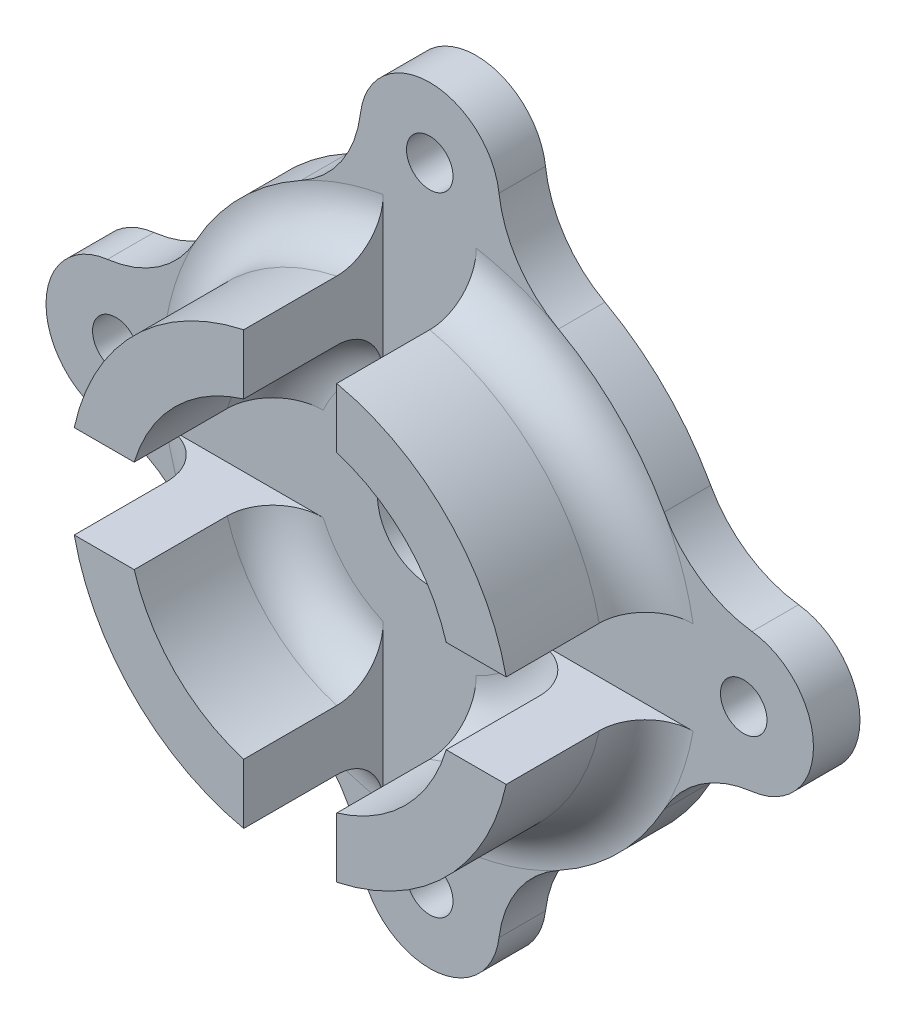
SolidWorks part; units mm, degrees
ref_plane "Front Plane" through (0, 0, 0) normal (0, 0, 1) x (1, 0, 0)
ref_plane "Top Plane" through (0, 0, 0) normal (0, 1, 0) x (1, 0, 0)
ref_plane "Right Plane" through (0, 0, 0) normal (1, 0, 0) x (0, 0, -1)
sketch "Sketch2" plane through (0, 0, 0) normal (0, 0, 1) x (1, 0, 0)
  line L0 (0, 9.5) -> (0, 0) construction
  line L1 (-2, 9.5) -> (-2, 0)
  line L2 (2, 9.5) -> (2, 0)
  line L3 (9.5, 2) -> (0, 2)
  line L4 (9.5, -2) -> (0, -2)
  line L5 (2, -9.5) -> (2, 0)
  line L6 (-2, -9.5) -> (-2, 0)
  line L7 (-9.5, -2) -> (0, -2)
  line L8 (-9.5, 2) -> (0, 2)
  circle A0 centre (0, 0) radius 2.25 construction
  circle A1 centre (0, 0) radius 9.5 construction
  circle A2 centre (0, 0) radius 2.25
  circle A3 centre (0, 0) radius 9.5
  circle A4 centre (0, 0) radius 7
  circle A5 centre (0, -13.5) radius 1 construction
  circle A6 centre (0, -13.5) radius 1
  arc A7 (5.5352, -10.0802) -> (2.9782, -13.8611) centre (7.9418, -14.463) ccw construction
  arc A8 (-2.9782, -13.8611) -> (2.9782, -13.8611) centre (0, -13.5) ccw construction
  arc A9 (-2.9782, -13.8611) -> (-5.5352, -10.0802) centre (-7.9418, -14.463) ccw construction
  arc A10 (-13.8611, 2.9782) -> (-13.8611, -2.9782) centre (-13.5, 0) ccw construction
  arc A11 (-10.0802, -5.5352) -> (-13.8611, -2.9782) centre (-14.463, -7.9418) ccw construction
  arc A12 (-13.8611, 2.9782) -> (-10.0802, 5.5352) centre (-14.463, 7.9418) ccw construction
  arc A13 (-5.5352, 10.0802) -> (-2.9782, 13.8611) centre (-7.9418, 14.463) ccw construction
  arc A14 (2.9782, 13.8611) -> (-2.9782, 13.8611) centre (0, 13.5) ccw construction
  arc A15 (2.9782, 13.8611) -> (5.5352, 10.0802) centre (7.9418, 14.463) ccw construction
  circle A16 centre (0, 0) radius 11.5 construction
  arc A17 (10.0802, 5.5352) -> (13.8611, 2.9782) centre (14.463, 7.9418) ccw construction
  arc A18 (13.8611, -2.9782) -> (10.0802, -5.5352) centre (14.463, -7.9418) ccw construction
  arc A19 (13.8611, -2.9782) -> (13.8611, 2.9782) centre (13.5, 0) ccw construction
  circle A20 centre (13.5, 0) radius 1 construction
  circle A21 centre (0, 13.5) radius 1 construction
  circle A22 centre (-13.5, 0) radius 1 construction
  arc A23 (5.5352, -10.0802) -> (2.9782, -13.8611) centre (7.9418, -14.463) ccw
  arc A24 (-2.9782, -13.8611) -> (2.9782, -13.8611) centre (0, -13.5) ccw
  arc A25 (-2.9782, -13.8611) -> (-5.5352, -10.0802) centre (-7.9418, -14.463) ccw
  arc A26 (-13.8611, 2.9782) -> (-13.8611, -2.9782) centre (-13.5, 0) ccw
  arc A27 (-10.0802, -5.5352) -> (-13.8611, -2.9782) centre (-14.463, -7.9418) ccw
  arc A28 (-13.8611, 2.9782) -> (-10.0802, 5.5352) centre (-14.463, 7.9418) ccw
  arc A29 (-5.5352, 10.0802) -> (-2.9782, 13.8611) centre (-7.9418, 14.463) ccw
  arc A30 (2.9782, 13.8611) -> (-2.9782, 13.8611) centre (0, 13.5) ccw
  arc A31 (2.9782, 13.8611) -> (5.5352, 10.0802) centre (7.9418, 14.463) ccw
  circle A32 centre (0, 0) radius 11.5
  arc A33 (10.0802, 5.5352) -> (13.8611, 2.9782) centre (14.463, 7.9418) ccw
  arc A34 (13.8611, -2.9782) -> (10.0802, -5.5352) centre (14.463, -7.9418) ccw
  arc A35 (13.8611, -2.9782) -> (13.8611, 2.9782) centre (13.5, 0) ccw
  circle A36 centre (13.5, 0) radius 1
  circle A37 centre (0, 13.5) radius 1
  circle A38 centre (-13.5, 0) radius 1
  point P27 (0, 0)
  dimension "D1" = 14
  dimension "D2" = 2
  dimension "D3" = 2
  dimension "D4" = 4
extrude "Boss-Extrude1" add sketch "Sketch2" along normal blind 2 contours A4 L1 A3 L8 | A3 L0 A4 L2 | L0 A3 L1 A4 | A4 L8 A3 L7 | A4 L7 A3 L6 | A4 L6 A3 L5 | A4 L5 A3 L4 | A4 L4 A3 L3 | A4 L3 A3 L2 | L7 A4 L6 | L6 A4 L5 L4 A2 L7 | L5 A4 L4 | L4 A4 L3 L2 A2 L5 | L3 A4 L2 | A4 L0 A2 L3 L2 | L0 A4 L1 L8 A2 | L1 A4 L8 | L8 A4 L7 L6 A2 L1 | A2 L8 L1 | A2 L2 L3 | A2 L4 L5 | A2 L6 L7 | A32 A28 A26 A27 A38 | A32 A25 A24 A23 A6 | A34 A35 A33 A32 A36 | A32 A31 A30 A29 A37 | A32 A3 region at (1.0052, 8.1658, 0) region at (-1.0052, 8.1658, 0) region at (1.001, 4.495, 0) region at (-1.001, 4.495, 0) region at (5.6126, 5.6126, 0) region at (-5.6126, 5.6126, 0) region at (3.8302, 3.8302, 0) region at (-3.8302, 3.8302, 0) region at (8.1658, 0, 0) region at (-8.1658, 0, 0) region at (1.7116, 1.7116, 0) region at (-1.7116, 1.7116, 0) region at (4.495, 0, 0) region at (-4.495, 0, 0) region at (-5.6126, -5.6126, 0) region at (-3.8302, -3.8302, 0) region at (5.6126, -5.6126, 0) region at (0, -8.1658, 0) region at (-1.7116, -1.7116, 0) region at (3.8302, -3.8302, 0) region at (0, -4.495, 0) region at (1.7116, -1.7116, 0) region at (3.6941, -11.5902, 0) region at (0, -11.1747, 0) region at (11.2634, -2.889, 0) region at (-11.5902, -3.6941, 0) region at (-3.6941, 11.5902, 0)
sketch "Sketch3" plane through (0, 0, 2) normal (0, 0, 1) x (1, 0, 0)
  line L0 (9.5, 2) -> (0, 2) construction
  line L1 (-9.5, 2) -> (0, 2) construction
  line L2 (2, 9.5) -> (2, 0) construction
  line L3 (2, -9.5) -> (2, 0) construction
  line L4 (-2, 9.5) -> (-2, 0) construction
  line L5 (-2, -9.5) -> (-2, 0) construction
  line L6 (9.5, -2) -> (0, -2) construction
  line L7 (-9.5, -2) -> (0, -2) construction
  line L8 (9.5, 2) -> (0, 2)
  line L9 (-9.5, 2) -> (0, 2)
  line L10 (2, 9.5) -> (2, 0)
  line L11 (2, -9.5) -> (2, 0)
  line L12 (-2, 9.5) -> (-2, 0)
  line L13 (-2, -9.5) -> (-2, 0)
  line L14 (9.5, -2) -> (0, -2)
  line L15 (-9.5, -2) -> (0, -2)
  arc A0 (5.5352, -10.0802) -> (2.9782, -13.8611) centre (7.9418, -14.463) ccw construction
  circle A1 centre (0, -13.5) radius 1
  circle A2 centre (0, -13.5) radius 1
  circle A3 centre (0, 0) radius 7
  circle A4 centre (0, 0) radius 7
  circle A5 centre (0, 0) radius 9.5
  circle A6 centre (0, 0) radius 9.5
  circle A7 centre (0, 0) radius 2.25
  circle A8 centre (0, 0) radius 2.25
  circle A9 centre (13.5, 0) radius 1
  circle A10 centre (13.5, 0) radius 1
  circle A11 centre (0, 0) radius 11.5
  circle A12 centre (0, 0) radius 11.5
  circle A13 centre (-13.5, 0) radius 1
  circle A14 centre (-13.5, 0) radius 1
  circle A15 centre (0, 13.5) radius 1
  circle A16 centre (0, 13.5) radius 1
  arc A17 (-2.9782, -13.8611) -> (2.9782, -13.8611) centre (0, -13.5) ccw construction
  arc A18 (-2.9782, -13.8611) -> (-5.5352, -10.0802) centre (-7.9418, -14.463) ccw construction
  arc A19 (-5.5352, 10.0802) -> (-2.9782, 13.8611) centre (-7.9418, 14.463) ccw construction
  arc A20 (2.9782, 13.8611) -> (-2.9782, 13.8611) centre (0, 13.5) ccw construction
  arc A21 (2.9782, 13.8611) -> (5.5352, 10.0802) centre (7.9418, 14.463) ccw construction
  arc A22 (-10.0802, -5.5352) -> (-13.8611, -2.9782) centre (-14.463, -7.9418) ccw construction
  arc A23 (-13.8611, 2.9782) -> (-13.8611, -2.9782) centre (-13.5, 0) ccw construction
  arc A24 (-13.8611, 2.9782) -> (-10.0802, 5.5352) centre (-14.463, 7.9418) ccw construction
  arc A25 (10.0802, 5.5352) -> (13.8611, 2.9782) centre (14.463, 7.9418) ccw construction
  arc A26 (13.8611, -2.9782) -> (13.8611, 2.9782) centre (13.5, 0) ccw construction
  arc A27 (13.8611, -2.9782) -> (10.0802, -5.5352) centre (14.463, -7.9418) ccw construction
  arc A28 (5.5352, -10.0802) -> (2.9782, -13.8611) centre (7.9418, -14.463) ccw
  arc A29 (-2.9782, -13.8611) -> (2.9782, -13.8611) centre (0, -13.5) ccw
  arc A30 (-2.9782, -13.8611) -> (-5.5352, -10.0802) centre (-7.9418, -14.463) ccw
  arc A31 (-5.5352, 10.0802) -> (-2.9782, 13.8611) centre (-7.9418, 14.463) ccw
  arc A32 (2.9782, 13.8611) -> (-2.9782, 13.8611) centre (0, 13.5) ccw
  arc A33 (2.9782, 13.8611) -> (5.5352, 10.0802) centre (7.9418, 14.463) ccw
  arc A34 (-10.0802, -5.5352) -> (-13.8611, -2.9782) centre (-14.463, -7.9418) ccw
  arc A35 (-13.8611, 2.9782) -> (-13.8611, -2.9782) centre (-13.5, 0) ccw
  arc A36 (-13.8611, 2.9782) -> (-10.0802, 5.5352) centre (-14.463, 7.9418) ccw
  arc A37 (10.0802, 5.5352) -> (13.8611, 2.9782) centre (14.463, 7.9418) ccw
  arc A38 (13.8611, -2.9782) -> (13.8611, 2.9782) centre (13.5, 0) ccw
  arc A39 (13.8611, -2.9782) -> (10.0802, -5.5352) centre (14.463, -7.9418) ccw
  dimension "D1" = 0
  dimension "D2" = 0
  dimension "D3" = 0
  dimension "D4" = 0
  dimension "D5" = 0
  dimension "D6" = 0
  dimension "D7" = 0
  dimension "D8" = 0
extrude "Boss-Extrude2" add sketch "Sketch3" along normal blind 6 contours L12 A6 L9 A4 | L8 A6 L10 A4 | L11 A6 L14 A4 | L15 A6 L13 A4 region at (5.6126, 5.6126, 2) region at (5.6126, -5.6126, 2) region at (-5.6126, 5.6126, 2) region at (-5.6126, -5.6126, 2)
fillet "Fillet1" radius 2 8 edges at (6.7175, -6.7175, 2) (4.9497, -4.9497, 2) (6.7175, 6.7175, 2) (4.9497, 4.9497, 2) (-4.9497, 4.9497, 2) (-6.7175, 6.7175, 2) (-4.9497, -4.9497, 2) (-6.7175, -6.7175, 2)
